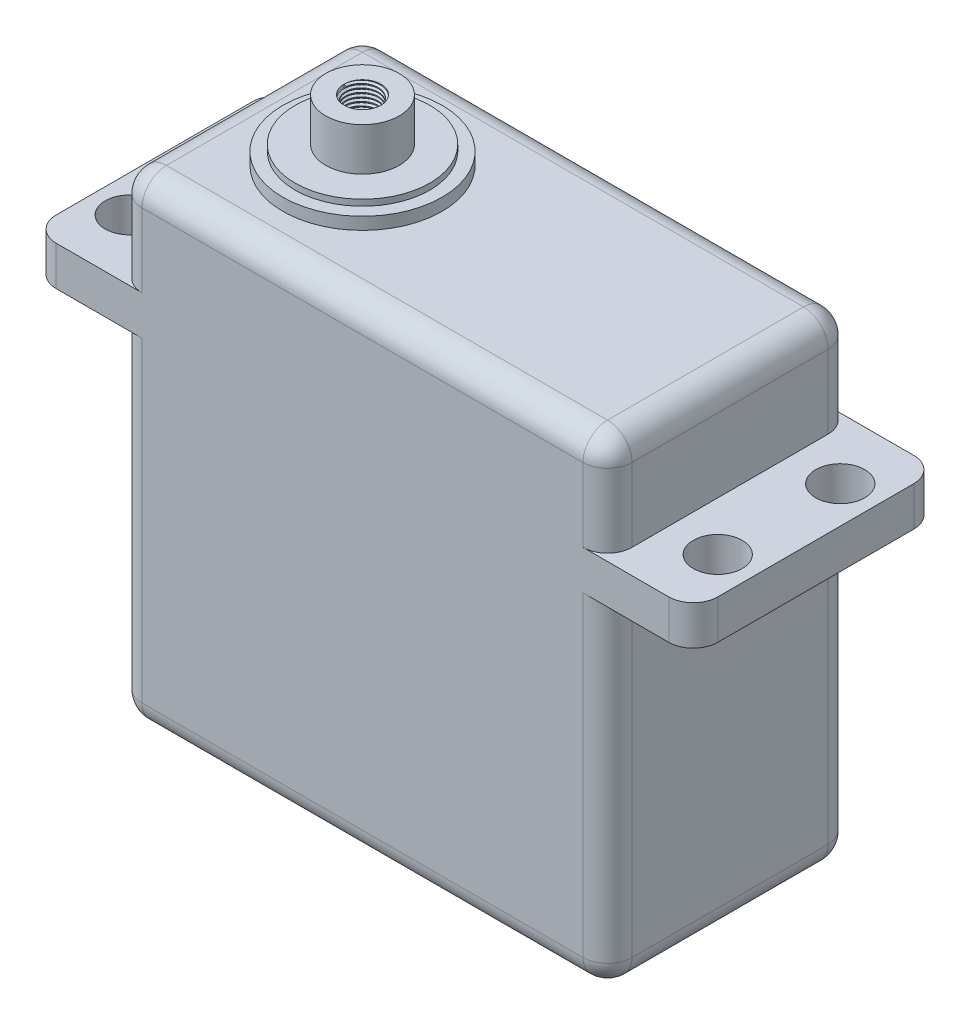
SolidWorks part; units mm, degrees
ref_plane "前视基准面" through (0, 0, 0) normal (0, 0, 1) x (1, 0, 0)
ref_plane "上视基准面" through (0, 0, 0) normal (0, 1, 0) x (1, 0, 0)
ref_plane "右视基准面" through (0, 0, 0) normal (1, 0, 0) x (0, 0, -1)
other "Configuration Table"
sketch "草图1" plane through (0, 0, 0) normal (0, 0, 1) x (1, 0, 0)
  line L1 (-59.4026, -1.7407) -> (-19.4026, -1.7407)
  line L2 (-59.4026, -1.7407) -> (-59.4026, -40.7407)
  line L3 (-59.4026, -40.7407) -> (-19.4026, -40.7407)
  line L4 (-19.4026, -1.7407) -> (-19.4026, -40.7407)
extrude "凸台-拉伸1" add sketch "草图1" along normal blind 20
sketch "草图3" plane through (-19.4026, 0, 0) normal (1, 0, 0) x (0, 0, -1)
  line L2 (-20, -9.7407) -> (0, -9.7407)
  line L4 (-20, -40.7407) -> (-20, -1.7407) construction
  line L5 (0, -40.7407) -> (0, -1.7407) construction
ref_plane "基准面1" through (0, -1.7407, 0) normal (0, 1, 0) x (1, 0, 0)
sketch "草图6" plane through (0, -1.7407, 0) normal (0, 1, 0) x (1, 0, 0)
  circle A0 centre (-49.4026, -10) radius 6.5
extrude "凸台-拉伸6" add sketch "草图6" along normal blind 1
ref_plane "基准面2" through (0, -0.7407, 0) normal (0, 1, 0) x (1, 0, 0)
sketch "草图7" plane through (0, -0.7407, 0) normal (0, 1, 0) x (1, 0, 0)
  circle A0 centre (-49.4026, -10) radius 5.5
extrude "凸台-拉伸7" add sketch "草图7" along normal blind 0.5
ref_plane "基准面3" through (0, -0.2407, 0) normal (0, 1, 0) x (1, 0, 0)
sketch "草图10" plane through (0, -0.2407, 0) normal (0, 1, 0) x (1, 0, 0)
  circle A0 centre (-49.4026, -10) radius 3
extrude "凸台-拉伸8" add sketch "草图10" along normal blind 3.5
ref_plane "基准面4" through (-19.4026, 0, 0) normal (1, 0, 0) x (0, 0, -1)
sketch "草图11" plane through (-19.4026, 0, 0) normal (1, 0, 0) x (0, 0, -1)
  line L0 (0, -40.7407) -> (0, -1.7407) construction
  line L1 (-20, -9.7407) -> (0, -9.7407)
  line L2 (-20, -9.7407) -> (-20, -12.9545)
  line L3 (-20, -12.9545) -> (0, -12.9545)
  line L4 (0, -9.7407) -> (0, -12.9545)
  dimension "D1" = 3.2138
extrude "凸台-拉伸9" add sketch "草图11" along normal blind 7
ref_plane "基准面5" through (0, -9.7407, 0) normal (0, 1, 0) x (1, 0, 0)
sketch "草图13" plane through (0, -9.7407, 0) normal (0, 1, 0) x (1, 0, 0)
  line L0 (-12.4026, -10) -> (-19.4026, -10)
  line L1 (-12.4026, 0) -> (-12.4026, -20) construction
  line L2 (-19.4026, -20) -> (-19.4026, 0) construction
  circle A0 centre (-15.4026, -15) radius 2
  circle A1 centre (-15.4026, -5) radius 2
  point P6 (0, 0)
  point P7 (0, 0)
  point P9 (0, 0)
extrude "切除-拉伸3" cut sketch "草图13" against normal blind 4 contours A0 | A1 region at (-15.4026, -9.7407, 15) region at (-15.4026, -9.7407, 5)
ref_plane "基准面6" through (-59.4026, 0, 0) normal (-1, 0, 0) x (0, 0, 1)
sketch "草图15" plane through (-59.4026, 0, 0) normal (-1, 0, 0) x (0, 0, 1)
  line L0 (20, -1.7407) -> (20, -40.7407) construction
  line L1 (0, -9.7407) -> (20, -9.7407)
  line L2 (0, -9.7407) -> (0, -12.9545)
  line L3 (0, -12.9545) -> (20, -12.9545)
  line L4 (20, -9.7407) -> (20, -12.9545)
extrude "凸台-拉伸11" add sketch "草图15" along normal blind 7
ref_plane "基准面7" through (0, -9.7407, 0) normal (0, 1, 0) x (1, 0, 0)
sketch "草图16" plane through (0, -9.7407, 0) normal (0, 1, 0) x (1, 0, 0)
  line L0 (-66.4026, -10) -> (-59.4026, -10)
  line L1 (-66.4026, -20) -> (-66.4026, 0) construction
  line L2 (-59.4026, 4.4) -> (-59.4026, -4.4) construction
  line L3 (-66.4026, -20) -> (-63.4026, -20)
  line L4 (-66.4026, -20) -> (-59.4026, -20) construction
  line L5 (-63.4026, -20) -> (-63.4026, -15)
  circle A0 centre (-63.4026, -15) radius 2
  circle A1 centre (-63.4026, -5) radius 2
extrude "切除-拉伸4" cut sketch "草图16" against normal blind 4 contours A1 | A0 region at (-62.0283, -9.7407, 16.3742) region at (-63.4026, -9.7407, 5)
fillet "圆角17" radius 2 1 edges at (-12.4026, -11.3476, 0)
fillet "圆角18" radius 2 1 edges at (-12.4026, -11.3476, 20)
fillet "圆角19" radius 2 1 edges at (-66.4026, -11.3476, 20)
fillet "圆角20" radius 2 1 edges at (-66.4026, -11.3476, 0)
fillet "圆角21" radius 2 1 edges at (-19.4026, -1.7407, 10) type face fillet first side face at (-49.4026, -1.7407, 3.5) second side face at (-19.4026, -5.7407, 10)
fillet "圆角22" radius 2 1 edges at (-40.4026, -1.7407, 0) type face fillet first side face at (-37.9861, -13.7746, 0) second side face at (-49.4026, -1.7407, 3.5)
fillet "圆角23" radius 2 1 edges at (-59.4026, -1.7407, 11) type face fillet first side face at (-59.4026, -5.2578, 8.3172) second side face at (-49.4026, -1.7407, 3.5)
fillet "圆角24" radius 2 1 edges at (-39.4026, -1.7407, 20) type face fillet first side face at (-49.4026, -1.7407, 3.5) second side face at (-39.4026, -13.0283, 20)
fillet "圆角25" radius 2 1 edges at (-59.4026, -26.8476, 20) type face fillet first side face at (-39.4026, -14.9786, 20) second side face at (-59.4026, -26.8476, 10)
fillet "圆角26" radius 2 1 edges at (-38.4026, -40.7407, 20) type face fillet first side face at (-39.0692, -14.9786, 20) second side face at (-43.0854, -40.7407, 11.6828)
fillet "圆角27" radius 2 1 edges at (-59.4026, -25.8476, 0) type face fillet first side face at (-59.4026, -25.8476, 9) second side face at (-40.819, -16.8383, 0)
fillet "圆角28" radius 2 2 edges at (-19.4026, -25.8476, 0) (-19.4026, -25.8476, 20) type face fillet first side face at (-19.4026, -30.95, 10) second side face at (-39.0692, -14.6453, 0) second side face at (-39.0692, -14.6453, 20)
ref_plane "基准面8" through (0, 3.2593, 0) normal (0, 1, 0) x (1, 0, 0)
sketch "草图24" plane through (0, 3.2593, 0) normal (0, 1, 0) x (1, 0, 0)
  circle A0 centre (-49.4026, -10) radius 1.5
extrude "切除-拉伸5" cut sketch "草图24" against normal blind 5
thread "螺纹线1" pitch 0.3175 method extrude profile "螺纹线轮廓1" start angle 0, offset 0, length 3, pitch 0.3175, diameter 3
ref_plane "基准面9" through (-50.9026, 3.2593, 10) normal (0, 0, 1) x (-1, 0, 0)
sketch "螺纹线轮廓1" plane through (-50.9026, 3.2593, 10) normal (0, 0, 1) x (-1, 0, 0)
  line L0 (0, 0) -> (0, 0.3175) construction
  line L11 (0, 0) -> (0, 0.2778)
  line L12 (0, 0.2778) -> (-0.1719, 0.1786)
  line L13 (-0.1719, 0.1786) -> (-0.1719, 0.0992)
  line L15 (-0.1719, 0.0992) -> (0, 0)
  line L17 (-0.1719, 0.1389) -> (0, 0.1389) construction
  point P2 (0, 0)
  dimension "Pitch" = 0.3175
  dimension "Profile_Angle" = 60
  dimension "Profile_Land" = 0.0794
  dimension "Profile_Height" = 0.1719
